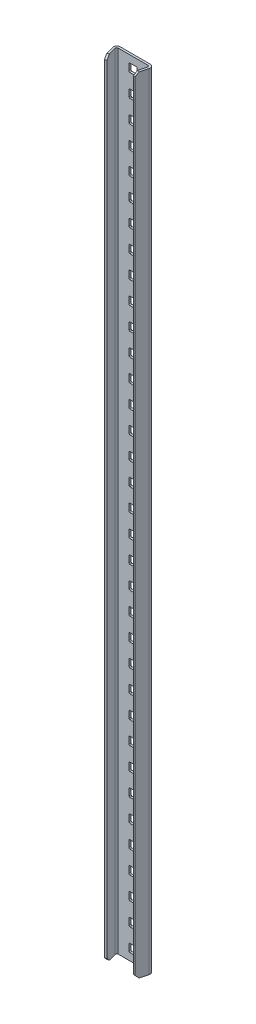
SolidWorks part; units mm, degrees
ref_plane "Front Plane" through (0, 0, 0) normal (0, 0, 1) x (1, 0, 0)
ref_plane "Top Plane" through (0, 0, 0) normal (0, 1, 0) x (1, 0, 0)
ref_plane "Right Plane" through (0, 0, 0) normal (1, 0, 0) x (0, 0, -1)
ref_plane "Plane1" through (0, 292.1, 0) normal (0, 1, 0) x (1, 0, 0)
sketch "Sketch1" plane through (0, 292.1, 0) normal (0, 1, 0) x (1, 0, 0)
  line L0 (9.1958, -2.1514) -> (7.4977, -8.4886)
  line L1 (7.4977, -8.4886) -> (8.6569, -8.7992)
  line L2 (8.6569, -8.7992) -> (10.3549, -2.462)
  line L3 (8.4657, 0) -> (-8.4657, 0)
  line L4 (-10.3549, -2.462) -> (-8.6569, -8.7992)
  line L5 (-8.6569, -8.7992) -> (-7.4977, -8.4886)
  line L6 (-7.4977, -8.4886) -> (-9.1958, -2.1514)
  line L7 (-8.4657, -1.2) -> (8.4657, -1.2)
  arc A0 (10.3549, -2.462) -> (8.4657, 0) centre (8.4657, -1.9558) ccw
  arc A1 (-8.4657, 0) -> (-10.3549, -2.462) centre (-8.4657, -1.9558) ccw
  arc A2 (-9.1958, -2.1514) -> (-8.4657, -1.2) centre (-8.4657, -1.9558) cw
  arc A3 (8.4657, -1.2) -> (9.1958, -2.1514) centre (8.4657, -1.9558) cw
extrude "Boss-Extrude1" add sketch "Sketch1" against normal blind 444.5
sketch "Sketch2" plane through (0, 0, 1.2) normal (0, 0, 1) x (1, 0, 0)
  line L0 (-2.3114, 148.3614) -> (-2.3114, 143.7386)
  line L1 (-2.3114, 143.7386) -> (2.3114, 143.7386)
  line L2 (2.3114, 143.7386) -> (2.3114, 148.3614)
  line L3 (2.3114, 148.3614) -> (-2.3114, 148.3614)
extrude "Cut-Extrude1" cut sketch "Sketch2" against normal through all
sketch "Sketch3" plane through (0, 0, 1.2) normal (0, 0, 1) x (1, 0, 0)
  line L0 (-2.3114, 135.6614) -> (-2.3114, 131.0386)
  line L1 (-2.3114, 131.0386) -> (2.3114, 131.0386)
  line L2 (2.3114, 131.0386) -> (2.3114, 135.6614)
  line L3 (2.3114, 135.6614) -> (-2.3114, 135.6614)
extrude "Cut-Extrude2" cut sketch "Sketch3" against normal through all
sketch "Sketch4" plane through (0, 0, 1.2) normal (0, 0, 1) x (1, 0, 0)
  line L0 (-2.3114, 122.9614) -> (-2.3114, 118.3386)
  line L1 (-2.3114, 118.3386) -> (2.3114, 118.3386)
  line L2 (2.3114, 118.3386) -> (2.3114, 122.9614)
  line L3 (2.3114, 122.9614) -> (-2.3114, 122.9614)
extrude "Cut-Extrude3" cut sketch "Sketch4" against normal through all
sketch "Sketch5" plane through (0, 0, 1.2) normal (0, 0, 1) x (1, 0, 0)
  line L0 (-2.3114, 110.2614) -> (-2.3114, 105.6386)
  line L1 (-2.3114, 105.6386) -> (2.3114, 105.6386)
  line L2 (2.3114, 105.6386) -> (2.3114, 110.2614)
  line L3 (2.3114, 110.2614) -> (-2.3114, 110.2614)
extrude "Cut-Extrude4" cut sketch "Sketch5" against normal through all
sketch "Sketch6" plane through (0, 0, 1.2) normal (0, 0, 1) x (1, 0, 0)
  line L0 (-2.3114, 97.5614) -> (-2.3114, 92.9386)
  line L1 (-2.3114, 92.9386) -> (2.3114, 92.9386)
  line L2 (2.3114, 92.9386) -> (2.3114, 97.5614)
  line L3 (2.3114, 97.5614) -> (-2.3114, 97.5614)
extrude "Cut-Extrude5" cut sketch "Sketch6" against normal through all
sketch "Sketch7" plane through (0, 0, 1.2) normal (0, 0, 1) x (1, 0, 0)
  line L0 (-2.3114, 84.8614) -> (-2.3114, 80.2386)
  line L1 (-2.3114, 80.2386) -> (2.3114, 80.2386)
  line L2 (2.3114, 80.2386) -> (2.3114, 84.8614)
  line L3 (2.3114, 84.8614) -> (-2.3114, 84.8614)
extrude "Cut-Extrude6" cut sketch "Sketch7" against normal through all
sketch "Sketch8" plane through (0, 0, 1.2) normal (0, 0, 1) x (1, 0, 0)
  line L0 (-2.3114, 72.1614) -> (-2.3114, 67.5386)
  line L1 (-2.3114, 67.5386) -> (2.3114, 67.5386)
  line L2 (2.3114, 67.5386) -> (2.3114, 72.1614)
  line L3 (2.3114, 72.1614) -> (-2.3114, 72.1614)
extrude "Cut-Extrude7" cut sketch "Sketch8" against normal through all
sketch "Sketch9" plane through (0, 0, 1.2) normal (0, 0, 1) x (1, 0, 0)
  line L0 (-2.3114, 59.4614) -> (-2.3114, 54.8386)
  line L1 (-2.3114, 54.8386) -> (2.3114, 54.8386)
  line L2 (2.3114, 54.8386) -> (2.3114, 59.4614)
  line L3 (2.3114, 59.4614) -> (-2.3114, 59.4614)
extrude "Cut-Extrude8" cut sketch "Sketch9" against normal through all
sketch "Sketch10" plane through (0, 0, 1.2) normal (0, 0, 1) x (1, 0, 0)
  line L0 (-2.3114, 46.7614) -> (-2.3114, 42.1386)
  line L1 (-2.3114, 42.1386) -> (2.3114, 42.1386)
  line L2 (2.3114, 42.1386) -> (2.3114, 46.7614)
  line L3 (2.3114, 46.7614) -> (-2.3114, 46.7614)
extrude "Cut-Extrude9" cut sketch "Sketch10" against normal through all
sketch "Sketch11" plane through (0, 0, 1.2) normal (0, 0, 1) x (1, 0, 0)
  line L0 (-2.3114, 34.0614) -> (-2.3114, 29.4386)
  line L1 (-2.3114, 29.4386) -> (2.3114, 29.4386)
  line L2 (2.3114, 29.4386) -> (2.3114, 34.0614)
  line L3 (2.3114, 34.0614) -> (-2.3114, 34.0614)
extrude "Cut-Extrude10" cut sketch "Sketch11" against normal through all
sketch "Sketch12" plane through (0, 0, 1.2) normal (0, 0, 1) x (1, 0, 0)
  line L0 (-2.3114, 21.3614) -> (-2.3114, 16.7386)
  line L1 (-2.3114, 16.7386) -> (2.3114, 16.7386)
  line L2 (2.3114, 16.7386) -> (2.3114, 21.3614)
  line L3 (2.3114, 21.3614) -> (-2.3114, 21.3614)
extrude "Cut-Extrude11" cut sketch "Sketch12" against normal through all
sketch "Sketch13" plane through (0, 0, 1.2) normal (0, 0, 1) x (1, 0, 0)
  line L0 (-2.3114, 8.6614) -> (-2.3114, 4.0386)
  line L1 (-2.3114, 4.0386) -> (2.3114, 4.0386)
  line L2 (2.3114, 4.0386) -> (2.3114, 8.6614)
  line L3 (2.3114, 8.6614) -> (-2.3114, 8.6614)
extrude "Cut-Extrude12" cut sketch "Sketch13" against normal through all
sketch "Sketch14" plane through (0, 0, 1.2) normal (0, 0, 1) x (1, 0, 0)
  line L0 (-2.3114, -4.0386) -> (-2.3114, -8.6614)
  line L1 (-2.3114, -8.6614) -> (2.3114, -8.6614)
  line L2 (2.3114, -8.6614) -> (2.3114, -4.0386)
  line L3 (2.3114, -4.0386) -> (-2.3114, -4.0386)
extrude "Cut-Extrude13" cut sketch "Sketch14" against normal through all
sketch "Sketch15" plane through (0, 0, 1.2) normal (0, 0, 1) x (1, 0, 0)
  line L0 (-2.3114, -131.0386) -> (-2.3114, -135.6614)
  line L1 (-2.3114, -135.6614) -> (2.3114, -135.6614)
  line L2 (2.3114, -135.6614) -> (2.3114, -131.0386)
  line L3 (2.3114, -131.0386) -> (-2.3114, -131.0386)
extrude "Cut-Extrude14" cut sketch "Sketch15" against normal through all
sketch "Sketch16" plane through (0, 0, 1.2) normal (0, 0, 1) x (1, 0, 0)
  line L0 (-2.3114, -143.7386) -> (-2.3114, -148.3614)
  line L1 (-2.3114, -148.3614) -> (2.3114, -148.3614)
  line L2 (2.3114, -148.3614) -> (2.3114, -143.7386)
  line L3 (2.3114, -143.7386) -> (-2.3114, -143.7386)
extrude "Cut-Extrude15" cut sketch "Sketch16" against normal through all
sketch "Sketch17" plane through (0, 0, 1.2) normal (0, 0, 1) x (1, 0, 0)
  line L0 (-2.3114, -118.3386) -> (-2.3114, -122.9614)
  line L1 (-2.3114, -122.9614) -> (2.3114, -122.9614)
  line L2 (2.3114, -122.9614) -> (2.3114, -118.3386)
  line L3 (2.3114, -118.3386) -> (-2.3114, -118.3386)
extrude "Cut-Extrude16" cut sketch "Sketch17" against normal through all
sketch "Sketch18" plane through (0, 0, 1.2) normal (0, 0, 1) x (1, 0, 0)
  line L0 (-2.3114, -105.6386) -> (-2.3114, -110.2614)
  line L1 (-2.3114, -110.2614) -> (2.3114, -110.2614)
  line L2 (2.3114, -110.2614) -> (2.3114, -105.6386)
  line L3 (2.3114, -105.6386) -> (-2.3114, -105.6386)
extrude "Cut-Extrude17" cut sketch "Sketch18" against normal through all
sketch "Sketch19" plane through (0, 0, 1.2) normal (0, 0, 1) x (1, 0, 0)
  line L0 (-2.3114, -92.9386) -> (-2.3114, -97.5614)
  line L1 (-2.3114, -97.5614) -> (2.3114, -97.5614)
  line L2 (2.3114, -97.5614) -> (2.3114, -92.9386)
  line L3 (2.3114, -92.9386) -> (-2.3114, -92.9386)
extrude "Cut-Extrude18" cut sketch "Sketch19" against normal through all
sketch "Sketch20" plane through (0, 0, 1.2) normal (0, 0, 1) x (1, 0, 0)
  line L0 (-2.3114, -80.2386) -> (-2.3114, -84.8614)
  line L1 (-2.3114, -84.8614) -> (2.3114, -84.8614)
  line L2 (2.3114, -84.8614) -> (2.3114, -80.2386)
  line L3 (2.3114, -80.2386) -> (-2.3114, -80.2386)
extrude "Cut-Extrude19" cut sketch "Sketch20" against normal through all
sketch "Sketch21" plane through (0, 0, 1.2) normal (0, 0, 1) x (1, 0, 0)
  line L0 (-2.3114, -67.5386) -> (-2.3114, -72.1614)
  line L1 (-2.3114, -72.1614) -> (2.3114, -72.1614)
  line L2 (2.3114, -72.1614) -> (2.3114, -67.5386)
  line L3 (2.3114, -67.5386) -> (-2.3114, -67.5386)
extrude "Cut-Extrude20" cut sketch "Sketch21" against normal through all
sketch "Sketch22" plane through (0, 0, 1.2) normal (0, 0, 1) x (1, 0, 0)
  line L0 (-2.3114, -54.8386) -> (-2.3114, -59.4614)
  line L1 (-2.3114, -59.4614) -> (2.3114, -59.4614)
  line L2 (2.3114, -59.4614) -> (2.3114, -54.8386)
  line L3 (2.3114, -54.8386) -> (-2.3114, -54.8386)
extrude "Cut-Extrude21" cut sketch "Sketch22" against normal through all
sketch "Sketch23" plane through (0, 0, 1.2) normal (0, 0, 1) x (1, 0, 0)
  line L0 (-2.3114, -42.1386) -> (-2.3114, -46.7614)
  line L1 (-2.3114, -46.7614) -> (2.3114, -46.7614)
  line L2 (2.3114, -46.7614) -> (2.3114, -42.1386)
  line L3 (2.3114, -42.1386) -> (-2.3114, -42.1386)
extrude "Cut-Extrude22" cut sketch "Sketch23" against normal through all
sketch "Sketch24" plane through (0, 0, 1.2) normal (0, 0, 1) x (1, 0, 0)
  line L0 (-2.3114, -29.4386) -> (-2.3114, -34.0614)
  line L1 (-2.3114, -34.0614) -> (2.3114, -34.0614)
  line L2 (2.3114, -34.0614) -> (2.3114, -29.4386)
  line L3 (2.3114, -29.4386) -> (-2.3114, -29.4386)
extrude "Cut-Extrude23" cut sketch "Sketch24" against normal through all
sketch "Sketch25" plane through (0, 0, 1.2) normal (0, 0, 1) x (1, 0, 0)
  line L0 (-2.3114, 161.0614) -> (-2.3114, 156.4386)
  line L1 (-2.3114, 156.4386) -> (2.3114, 156.4386)
  line L2 (2.3114, 156.4386) -> (2.3114, 161.0614)
  line L3 (2.3114, 161.0614) -> (-2.3114, 161.0614)
extrude "Cut-Extrude24" cut sketch "Sketch25" against normal through all
sketch "Sketch26" plane through (0, 0, 1.2) normal (0, 0, 1) x (1, 0, 0)
  line L0 (-2.3114, 173.7614) -> (-2.3114, 169.1386)
  line L1 (-2.3114, 169.1386) -> (2.3114, 169.1386)
  line L2 (2.3114, 169.1386) -> (2.3114, 173.7614)
  line L3 (2.3114, 173.7614) -> (-2.3114, 173.7614)
extrude "Cut-Extrude25" cut sketch "Sketch26" against normal through all
sketch "Sketch27" plane through (0, 0, 1.2) normal (0, 0, 1) x (1, 0, 0)
  line L0 (-2.3114, 186.4614) -> (-2.3114, 181.8386)
  line L1 (-2.3114, 181.8386) -> (2.3114, 181.8386)
  line L2 (2.3114, 181.8386) -> (2.3114, 186.4614)
  line L3 (2.3114, 186.4614) -> (-2.3114, 186.4614)
extrude "Cut-Extrude26" cut sketch "Sketch27" against normal through all
sketch "Sketch28" plane through (0, 0, 1.2) normal (0, 0, 1) x (1, 0, 0)
  line L0 (-2.3114, 199.1614) -> (-2.3114, 194.5386)
  line L1 (-2.3114, 194.5386) -> (2.3114, 194.5386)
  line L2 (2.3114, 194.5386) -> (2.3114, 199.1614)
  line L3 (2.3114, 199.1614) -> (-2.3114, 199.1614)
extrude "Cut-Extrude27" cut sketch "Sketch28" against normal through all
sketch "Sketch29" plane through (0, 0, 1.2) normal (0, 0, 1) x (1, 0, 0)
  line L0 (-2.3114, 211.8614) -> (-2.3114, 207.2386)
  line L1 (-2.3114, 207.2386) -> (2.3114, 207.2386)
  line L2 (2.3114, 207.2386) -> (2.3114, 211.8614)
  line L3 (2.3114, 211.8614) -> (-2.3114, 211.8614)
extrude "Cut-Extrude28" cut sketch "Sketch29" against normal through all
sketch "Sketch30" plane through (0, 0, 1.2) normal (0, 0, 1) x (1, 0, 0)
  line L0 (-2.3114, 224.5614) -> (-2.3114, 219.9386)
  line L1 (-2.3114, 219.9386) -> (2.3114, 219.9386)
  line L2 (2.3114, 219.9386) -> (2.3114, 224.5614)
  line L3 (2.3114, 224.5614) -> (-2.3114, 224.5614)
extrude "Cut-Extrude29" cut sketch "Sketch30" against normal through all
sketch "Sketch31" plane through (0, 0, 1.2) normal (0, 0, 1) x (1, 0, 0)
  line L0 (-2.3114, 237.2614) -> (-2.3114, 232.6386)
  line L1 (-2.3114, 232.6386) -> (2.3114, 232.6386)
  line L2 (2.3114, 232.6386) -> (2.3114, 237.2614)
  line L3 (2.3114, 237.2614) -> (-2.3114, 237.2614)
extrude "Cut-Extrude30" cut sketch "Sketch31" against normal through all
sketch "Sketch32" plane through (0, 0, 1.2) normal (0, 0, 1) x (1, 0, 0)
  line L0 (-2.3114, 249.9614) -> (-2.3114, 245.3386)
  line L1 (-2.3114, 245.3386) -> (2.3114, 245.3386)
  line L2 (2.3114, 245.3386) -> (2.3114, 249.9614)
  line L3 (2.3114, 249.9614) -> (-2.3114, 249.9614)
extrude "Cut-Extrude31" cut sketch "Sketch32" against normal through all
sketch "Sketch33" plane through (0, 0, 1.2) normal (0, 0, 1) x (1, 0, 0)
  line L0 (-2.3114, 262.6614) -> (-2.3114, 258.0386)
  line L1 (-2.3114, 258.0386) -> (2.3114, 258.0386)
  line L2 (2.3114, 258.0386) -> (2.3114, 262.6614)
  line L3 (2.3114, 262.6614) -> (-2.3114, 262.6614)
extrude "Cut-Extrude32" cut sketch "Sketch33" against normal through all
sketch "Sketch34" plane through (0, 0, 1.2) normal (0, 0, 1) x (1, 0, 0)
  line L0 (-2.3114, 275.3614) -> (-2.3114, 270.7386)
  line L1 (-2.3114, 270.7386) -> (2.3114, 270.7386)
  line L2 (2.3114, 270.7386) -> (2.3114, 275.3614)
  line L3 (2.3114, 275.3614) -> (-2.3114, 275.3614)
extrude "Cut-Extrude33" cut sketch "Sketch34" against normal through all
sketch "Sketch35" plane through (0, 0, 1.2) normal (0, 0, 1) x (1, 0, 0)
  line L0 (-2.3114, 288.0614) -> (-2.3114, 283.4386)
  line L1 (-2.3114, 283.4386) -> (2.3114, 283.4386)
  line L2 (2.3114, 283.4386) -> (2.3114, 288.0614)
  line L3 (2.3114, 288.0614) -> (-2.3114, 288.0614)
extrude "Cut-Extrude34" cut sketch "Sketch35" against normal through all
sketch "Sketch36" plane through (0, 0, 0) normal (0, 0, -1) x (-1, 0, 0)
  line L0 (-2.3114, -21.3614) -> (2.3114, -21.3614)
  line L1 (2.3114, -21.3614) -> (2.3114, -16.7386)
  line L2 (2.3114, -16.7386) -> (-2.3114, -16.7386)
  line L3 (-2.3114, -16.7386) -> (-2.3114, -21.3614)
extrude "Cut-Extrude35" cut sketch "Sketch36" against normal through all
chamfer "Chamfer1" distance 1.905 angle 45 4 edges at (-8.0773, 292.1, 8.6439) (-8.0773, -152.4, 8.6439) (8.0773, 292.1, 8.6439) (8.0773, -152.4, 8.6439)
fillet "Fillet1" radius 0.508 140 edges at (2.3114, 110.2614, 0.6) (2.3114, 8.6614, 0.6) (2.3114, 186.4614, 0.6) (2.3114, -21.3614, 0.6) (2.3114, 59.4614, 0.6) (-2.3114, -21.3614, 0.6) (2.3114, 211.8614, 0.6) (-2.3114, -16.7386, 0.6) (2.3114, 161.0614, 0.6) (2.3114, -16.7386, 0.6) (2.3114, 34.0614, 0.6) (2.3114, -34.0614, 0.6) (2.3114, 84.8614, 0.6) (-2.3114, -34.0614, 0.6) (2.3114, 135.6614, 0.6) (-2.3114, -29.4386, 0.6) (2.3114, 199.1614, 0.6) (2.3114, -29.4386, 0.6) (2.3114, 173.7614, 0.6) (2.3114, -46.7614, 0.6) (2.3114, -4.0386, 0.6) (-2.3114, -46.7614, 0.6) (2.3114, 21.3614, 0.6) (-2.3114, -42.1386, 0.6) (2.3114, 46.7614, 0.6) (2.3114, -42.1386, 0.6) (2.3114, 72.1614, 0.6) (2.3114, -59.4614, 0.6) (2.3114, 97.5614, 0.6) (-2.3114, -59.4614, 0.6) (2.3114, 122.9614, 0.6) (-2.3114, -54.8386, 0.6) (2.3114, 148.3614, 0.6) (2.3114, -54.8386, 0.6) (-2.3114, 194.5386, 0.6) (2.3114, -72.1614, 0.6) (-2.3114, 181.8386, 0.6) (-2.3114, -72.1614, 0.6) (-2.3114, 169.1386, 0.6) (-2.3114, -67.5386, 0.6) (-2.3114, 156.4386, 0.6) (2.3114, -67.5386, 0.6) (-2.3114, -8.6614, 0.6) (2.3114, -84.8614, 0.6) (-2.3114, 4.0386, 0.6) (-2.3114, -84.8614, 0.6) (-2.3114, 16.7386, 0.6) (-2.3114, -80.2386, 0.6) (-2.3114, 29.4386, 0.6) (2.3114, -80.2386, 0.6) (-2.3114, 42.1386, 0.6) (2.3114, -97.5614, 0.6) (-2.3114, 54.8386, 0.6) (-2.3114, -97.5614, 0.6) (-2.3114, 67.5386, 0.6) (-2.3114, -92.9386, 0.6) (-2.3114, 80.2386, 0.6) (2.3114, -92.9386, 0.6) (-2.3114, 92.9386, 0.6) (2.3114, -110.2614, 0.6) (-2.3114, 105.6386, 0.6) (-2.3114, -110.2614, 0.6) (-2.3114, 118.3386, 0.6) (-2.3114, -105.6386, 0.6) (-2.3114, 131.0386, 0.6) (2.3114, -105.6386, 0.6) (-2.3114, 143.7386, 0.6) (2.3114, -122.9614, 0.6) (-2.3114, 211.8614, 0.6) (-2.3114, -122.9614, 0.6) (2.3114, 194.5386, 0.6) (-2.3114, -118.3386, 0.6) (-2.3114, 199.1614, 0.6) (2.3114, -118.3386, 0.6) (2.3114, 181.8386, 0.6) (-2.3114, -148.3614, 0.6) (-2.3114, 186.4614, 0.6) (-2.3114, -143.7386, 0.6) (2.3114, 169.1386, 0.6) (2.3114, -143.7386, 0.6) (-2.3114, 173.7614, 0.6) (2.3114, -148.3614, 0.6) (2.3114, 156.4386, 0.6) (-2.3114, -135.6614, 0.6) (-2.3114, 161.0614, 0.6) (-2.3114, -131.0386, 0.6) (2.3114, -8.6614, 0.6) (2.3114, -131.0386, 0.6) (-2.3114, -4.0386, 0.6) (2.3114, -135.6614, 0.6) (2.3114, 4.0386, 0.6) (2.3114, 283.4386, 0.6) (-2.3114, 8.6614, 0.6) (-2.3114, 283.4386, 0.6) (2.3114, 16.7386, 0.6) (-2.3114, 288.0614, 0.6) (-2.3114, 21.3614, 0.6) (2.3114, 288.0614, 0.6) (2.3114, 29.4386, 0.6) (2.3114, 270.7386, 0.6) (-2.3114, 34.0614, 0.6) (-2.3114, 270.7386, 0.6) (2.3114, 42.1386, 0.6) (-2.3114, 275.3614, 0.6) (-2.3114, 46.7614, 0.6) (2.3114, 275.3614, 0.6) (2.3114, 54.8386, 0.6) (2.3114, 258.0386, 0.6) (-2.3114, 59.4614, 0.6) (-2.3114, 258.0386, 0.6) (2.3114, 67.5386, 0.6) (-2.3114, 262.6614, 0.6) (-2.3114, 72.1614, 0.6) (2.3114, 262.6614, 0.6) (2.3114, 80.2386, 0.6) (2.3114, 245.3386, 0.6) (-2.3114, 84.8614, 0.6) (-2.3114, 245.3386, 0.6) (2.3114, 92.9386, 0.6) (-2.3114, 249.9614, 0.6) (-2.3114, 97.5614, 0.6) (2.3114, 249.9614, 0.6) (2.3114, 105.6386, 0.6) (2.3114, 232.6386, 0.6) (-2.3114, 110.2614, 0.6) (-2.3114, 232.6386, 0.6) (2.3114, 118.3386, 0.6) (-2.3114, 237.2614, 0.6) (-2.3114, 122.9614, 0.6) (2.3114, 237.2614, 0.6) (2.3114, 131.0386, 0.6) (2.3114, 219.9386, 0.6) (-2.3114, 135.6614, 0.6) (-2.3114, 219.9386, 0.6) (2.3114, 143.7386, 0.6) (-2.3114, 224.5614, 0.6) (-2.3114, 148.3614, 0.6) (2.3114, 207.2386, 0.6) (-2.3114, 207.2386, 0.6) (2.3114, 224.5614, 0.6) tangent propagation no
